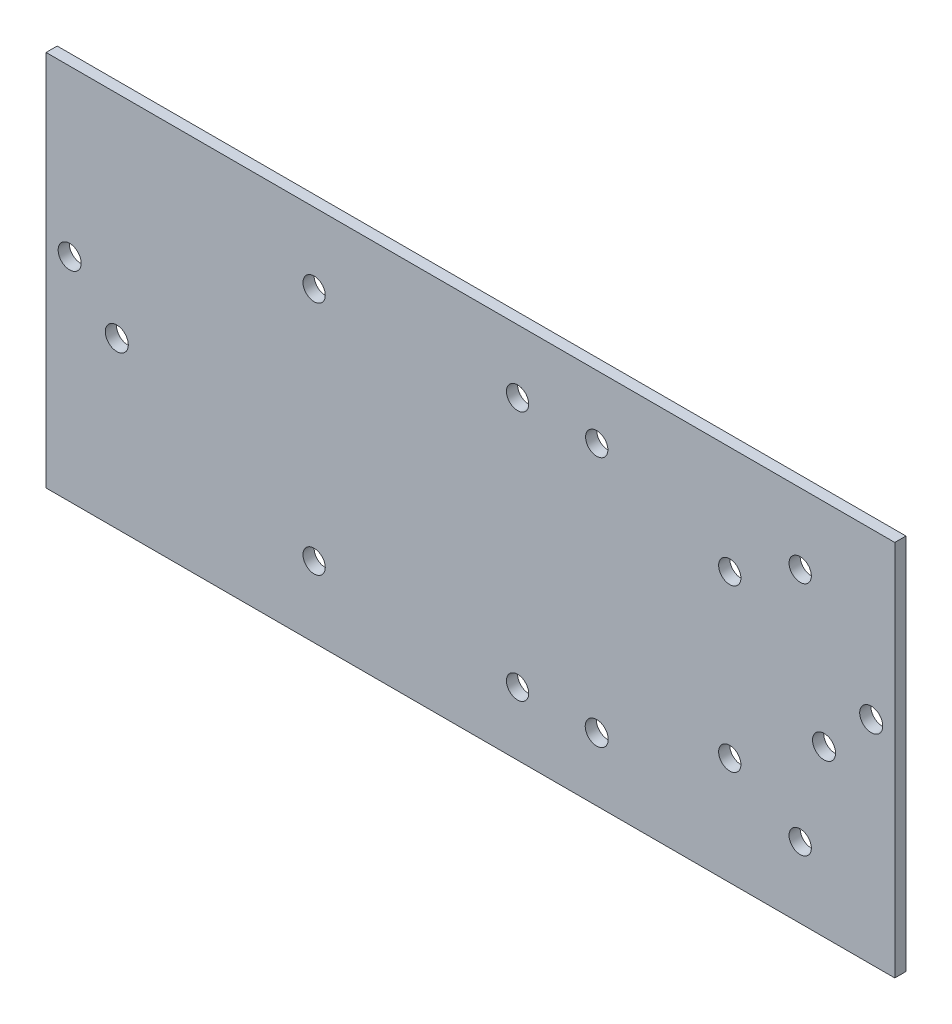
SolidWorks part; units mm, degrees
ref_plane "Front" through (0, 0, 0) normal (0, 0, 1) x (1, 0, 0)
ref_plane "Top" through (0, 0, 0) normal (0, 1, 0) x (1, 0, 0)
ref_plane "Right" through (0, 0, 0) normal (1, 0, 0) x (0, 0, -1)
sketch "Sketch1" plane through (0, 0, 0) normal (0, 0, 1) x (1, 0, 0)
  line L1 (-57.15, 25.4) -> (57.15, 25.4)
  line L2 (-57.15, 25.4) -> (-57.15, -25.4)
  line L3 (-57.15, -25.4) -> (57.15, -25.4)
  line L4 (57.15, 25.4) -> (57.15, -25.4)
extrude "Extrude1" add sketch "Sketch1" along normal blind 1.5
sketch "Sketch2" plane through (0, 0, 1.5) normal (0, 0, 1) x (1, 0, 0)
  circle A0 centre (-53.975, 3.175) radius 1.55
  circle A1 centre (-47.625, -3.175) radius 1.55
  circle A2 centre (53.975, 3.175) radius 1.55
  circle A3 centre (47.625, -3.175) radius 1.55
extrude "Cut-Extrude1" cut sketch "Sketch2" against normal through all
sketch "Sketch3" plane through (0, 0, 1.5) normal (0, 0, 1) x (1, 0, 0)
  circle A0 centre (6.35, 16.875) radius 1.5
  circle A1 centre (34.925, 10.875) radius 1.5
  circle A2 centre (6.35, -16.875) radius 1.5
  circle A3 centre (34.925, -10.875) radius 1.5
  circle A4 centre (17.01, 16.875) radius 1.5
  circle A5 centre (17.01, -16.875) radius 1.55
  circle A7 centre (44.41, 15.875) radius 1.5
  circle A8 centre (44.41, -15.875) radius 1.5
  circle A9 centre (-21.05, 15.875) radius 1.5
  circle A10 centre (-21.05, -15.875) radius 1.5
extrude "Cut-Extrude2" cut sketch "Sketch3" against normal through all
